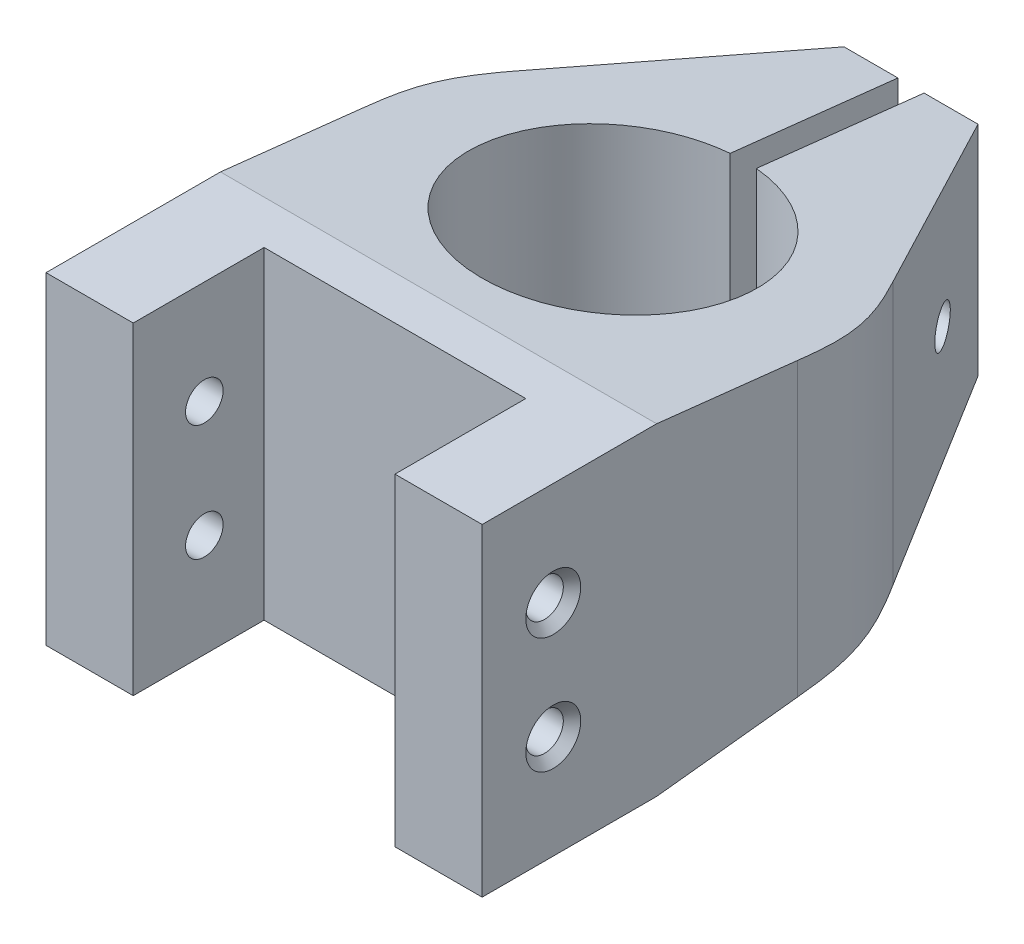
SolidWorks part; units mm, degrees
material "ABS PC"
ref_plane "Front Plane" through (0, 0, 0) normal (0, 0, 1) x (1, 0, 0)
ref_plane "Top Plane" through (0, 0, 0) normal (0, 1, 0) x (1, 0, 0)
ref_plane "Right Plane" through (0, 0, 0) normal (1, 0, 0) x (0, 0, -1)
sketch "Sketch1" plane through (0, 0, 0) normal (0, 1, 0) x (1, 0, 0)
  line L0 (0, -25) -> (15, -25)
  line L1 (15, -25) -> (15, -40)
  line L2 (15, -40) -> (25, -40)
  line L3 (25, -40) -> (25, 4.16)
  line L4 (25, 4.16) -> (7.6795, 34.16)
  line L5 (7.6795, 34.16) -> (1.5, 34.16)
  line L6 (1.5, 34.16) -> (1.5, 14.9248)
  line L7 (0, -25) -> (0, -15)
  line L8 (0, -15) -> (0, 0) construction
  arc A0 (0, -15) -> (1.5, 14.9248) centre (0, 0) ccw
  dimension "D1" = 30
  dimension "D6" = 19.16
  dimension "D2" = 30
  dimension "D3" = 50
  dimension "D4" = 15
  dimension "D5" = 10
  dimension "D7" = 1.5
  dimension "D8" = 150
  dimension "D9" = 30
extrude "Boss-Extrude1" add sketch "Sketch1" along normal blind 25
mirror "Mirror1" about plane through (0, 25, 25) normal (1, 0, 0) of bodies 101
sketch "Sketch8" plane through (0, 25, 0) normal (0, 1, 0) x (1, 0, 0)
  line L0 (15, -40) -> (25, -40) construction
  line L1 (-15, -40) -> (-25, -40) construction
  line L2 (-15, -25) -> (-15, -40) construction
  line L3 (-15, -25) -> (15, -25) construction
  line L4 (15, -40) -> (25, -40)
  line L5 (-15, -40) -> (-25, -40)
  line L6 (-15, -25) -> (-15, -40)
  line L7 (-15, -25) -> (15, -25)
  line L8 (15, -25) -> (15, -40) construction
  line L9 (15, -25) -> (15, -40)
  line L10 (-25, -20) -> (-25, -40)
  line L11 (-25, -20) -> (25, -20)
  line L12 (25, -20) -> (25, -40)
  point P7 (23.1865, -40)
  point P10 (0, 0)
  point P12 (-23.6007, -40)
  dimension "D1" = 5
extrude "Boss-Extrude2" add sketch "Sketch8" along normal blind 6
sketch "Sketch10" plane through (0, 0, 0) normal (1, 0, 0) x (0, 0, -1)
  line L0 (-20, 31) -> (34.16, 25)
  line L1 (34.16, 25) -> (-20, 25)
  line L2 (-20, 25) -> (-20, 31)
  line L3 (-20, 31) -> (-20, 25) construction
  point P4 (-20, 30.6714)
extrude "Boss-Extrude3" add sketch "Sketch10" along normal up to surface and the other way up to surface up to face at (25, 18.6667, 18.6133) other way up to face at (-25, 18.6667, 18.6133)
ref_plane "Plane1" through (0, 12.5, 0) normal (0, -1, 0) x (-1, 0, 0)
sketch "Sketch11" plane through (0, 12.5, 0) normal (0, -1, 0) x (-1, 0, 0)
  line L0 (-25, 34.16) -> (-25, 4.16) construction
  line L1 (-25, 4.16) -> (-7.6795, 34.16) construction
  line L2 (-7.6795, 34.16) -> (-25, 34.16) construction
  line L3 (1.5, 34.16) -> (-1.5, 34.16)
  line L4 (-1.5, 34.16) -> (-1.5, 14.9248)
  line L5 (1.5, 14.9248) -> (1.5, 34.16)
  line L6 (1.5, 34.16) -> (-1.5, 34.16)
  line L7 (-1.5, 34.16) -> (-1.5, 14.9248)
  line L8 (1.5, 14.9248) -> (1.5, 34.16)
  line L9 (25, 34.16) -> (7.6795, 34.16) construction
  line L10 (7.6795, 34.16) -> (25, 4.16) construction
  line L11 (25, 4.16) -> (25, 34.16) construction
  line L12 (-25, 34.16) -> (-25, 4.16)
  line L13 (-25, 4.16) -> (-7.6795, 34.16)
  line L14 (-7.6795, 34.16) -> (-25, 34.16)
  line L15 (25, 34.16) -> (7.6795, 34.16)
  line L16 (7.6795, 34.16) -> (25, 4.16)
  line L17 (25, 4.16) -> (25, 34.16)
  arc A1 (-1.5, 14.9248) -> (1.5, 14.9248) centre (0, 0) ccw
  arc A2 (-1.5, 14.9248) -> (1.5, 14.9248) centre (0, 0) ccw
  dimension "D1" = 0
mirror "Mirror2" about plane through (0, 12.5, 0) normal (0, -1, 0) of "Boss-Extrude2", "Boss-Extrude3"
extrude "Cut-Extrude5" cut sketch "Sketch11" against normal through all both and the other way through all
fillet "Fillet1" radius 30 2 edges at (-25, 12.5, -4.16) (25, 12.5, -4.16) curvature continuous yes
sketch "Sketch2" plane through (-25, 0, 0) normal (-1, 0, 0) x (0, 0, 1)
  line L0 (40, 31) -> (40, -6) construction
  line L5 (31.85, 19.15) -> (31.85, 25) construction
  line L6 (40, 25) -> (3.8785, 25) construction
  line L7 (31.85, 5.85) -> (31.85, 0) construction
  line L8 (40, 0) -> (3.8785, 0) construction
  circle A0 centre (31.85, 19.15) radius 2.15
  circle A1 centre (31.85, 5.85) radius 2.15
  dimension "D1" = 4.3
  dimension "D2" = 6
  dimension "D3" = 9
extrude "Cut-Extrude1" cut sketch "Sketch2" against normal through all
sketch "Sketch6" plane through (0, 0, 0) normal (1, 0, 0) x (0, 0, -1)
  line L1 (24.5424, 0) -> (24.5424, 25) construction
  line L2 (14.9248, 12.5) -> (34.16, 12.5) construction
  line L3 (34.16, 25) -> (14.9248, 25) construction
  line L4 (34.16, 25) -> (34.16, 0) construction
  line L5 (34.16, 0) -> (14.9248, 0) construction
  line L6 (14.9248, 27.1309) -> (14.9248, -2.1309) construction
  circle A0 centre (24.5424, 12.5) radius 2.1
  circle A1 centre (24.5424, 12.5) radius 3.5
  point P5 (24.5424, 12.5)
  point P9 (24.5424, 12.5)
  dimension "D1" = 4.2
  dimension "D2" = 7
extrude "Cut-Extrude2" cut sketch "Sketch6" against normal through all both and the other way through all contours A0 region at (0, 12.5, -24.5424)
extrude "Cut-Extrude3" cut sketch "Sketch6<3>" against normal up to surface (3.532 mm away) from vertex contours A1 rebuild error yes up to face at (14.4446, 12.5, -22.4424) starting at point (7.6795, 25, -34.16)
sketch "Sketch6<3>" plane through (0, 0, 0) normal (1, 0, 0) x (0, 0, -1) same geometry as "Sketch6"
fillet "Fillet2" radius 1 rebuild error yes
chamfer "Chamfer3" distance 1 angle 45 5 edges at (-25, 5.85, 34) (-25, 19.15, 34) (25, 5.85, 34) (25, 19.15, 34) (-1.5, 12.5, -22.4424)
sketch "Sketch7" plane through (-1.5, 0, 0) normal (1, 0, 0) x (0, 0, -1)
  line L1 (24.5424, 8.3431) -> (28.1424, 10.4215)
  line L2 (28.1424, 10.4215) -> (28.1424, 14.5785)
  line L3 (28.1424, 14.5785) -> (24.5424, 16.6569)
  line L4 (24.5424, 16.6569) -> (20.9424, 14.5785)
  line L5 (20.9424, 14.5785) -> (20.9424, 10.4215)
  line L6 (20.9424, 10.4215) -> (24.5424, 8.3431)
  circle A0 centre (24.5424, 12.5) radius 3.6 construction
  dimension "D1" = 7.2
extrude "Cut-Extrude4" cut sketch "Sketch7" against normal through all from offset 6 offset against normal yes
chamfer "Chamfer4" distance 0.5 angle 45 6 edges at (-12.193, 9.3823, -26.3424) (-11.1538, 12.5, -28.1424) (-12.193, 15.6177, -26.3424) (-14.2714, 15.6177, -22.7424) (-15.3107, 12.5, -20.9424) (-14.2714, 9.3823, -22.7424) first distance on face at (-9.8465, 9.3823, -26.3424) first distance on face at (-9.3269, 12.5, -28.1424) first distance on face at (-9.8465, 15.6177, -26.3424) first distance on face at (-10.8857, 15.6177, -22.7424) first distance on face at (-11.4053, 12.5, -20.9424) first distance on face at (-10.8857, 9.3823, -22.7424)
